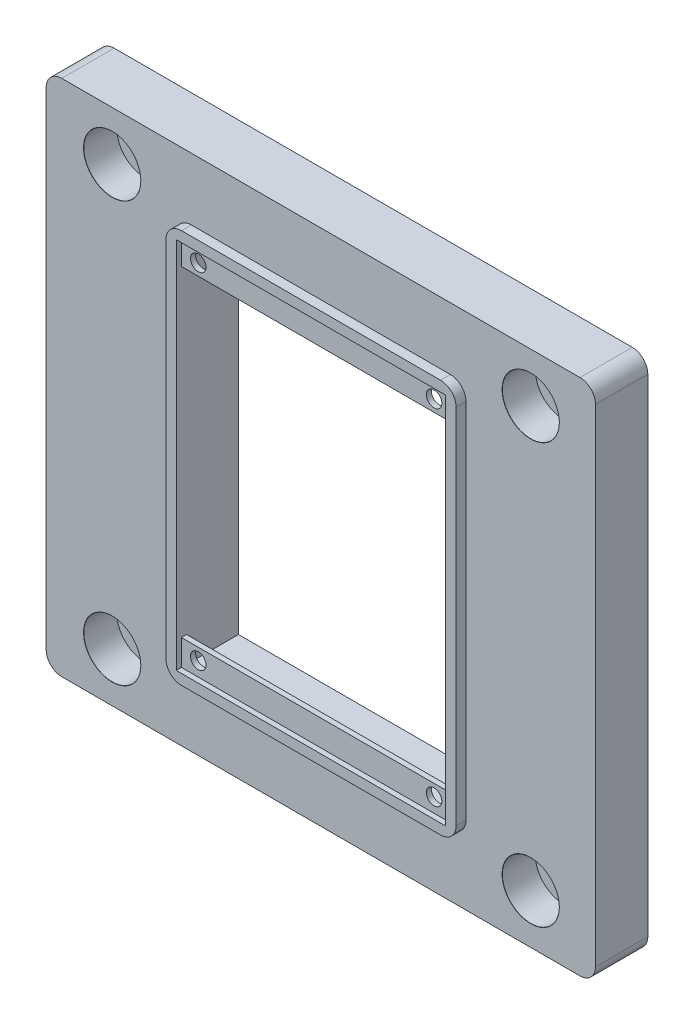
SolidWorks part; units mm, degrees
ref_plane "Front Plane" through (0, 0, 0) normal (1, 0, 0) x (0, 1, 0)
ref_plane "Top Plane" through (0, 0, 0) normal (0, 0, 1) x (0, 1, 0)
ref_plane "Right Plane" through (0, 0, 0) normal (0, 1, 0) x (-1, 0, 0)
sketch "Sketch1" plane through (0, 0, 0) normal (0, 0, 1) x (0, 1, 0)
  line L0 (33.4102, -36.8483) -> (45.4102, -61.8483)
  line L1 (-39.5237, 16.1988) -> (30.4763, 16.1988)
  line L2 (-39.5237, 16.1988) -> (-39.5237, -33.8012)
  line L3 (-39.5237, -33.8012) -> (30.4763, -33.8012)
  line L4 (30.4763, 16.1988) -> (30.4763, -33.8012)
  line L5 (-40.5898, 17.1517) -> (31.4102, 17.1517)
  line L6 (-40.5898, 17.1517) -> (-40.5898, -34.8483)
  line L7 (-40.5898, -34.8483) -> (31.4102, -34.8483)
  line L8 (31.4102, 17.1517) -> (31.4102, -34.8483)
  line L9 (-40.5898, 17.1517) -> (31.4102, -34.8483) construction
  line L10 (-40.5898, -34.8483) -> (31.4102, 17.1517) construction
  line L11 (-42.5898, -36.8483) -> (33.4102, -36.8483)
  line L12 (-42.5898, -36.8483) -> (-42.5898, 19.1517)
  line L13 (-42.5898, 19.1517) -> (33.4102, 19.1517)
  line L14 (33.4102, -36.8483) -> (33.4102, 19.1517)
  line L15 (-42.5898, -36.8483) -> (33.4102, 19.1517) construction
  line L16 (-42.5898, 19.1517) -> (33.4102, -36.8483) construction
  line L17 (-54.5898, 44.1517) -> (45.4102, 44.1517)
  line L18 (-54.5898, 44.1517) -> (-54.5898, -61.8483)
  line L19 (-54.5898, -61.8483) -> (45.4102, -61.8483)
  line L20 (45.4102, 44.1517) -> (45.4102, -61.8483)
  line L21 (-54.5898, 44.1517) -> (45.4102, -61.8483) construction
  line L22 (-54.5898, -61.8483) -> (45.4102, 44.1517) construction
  line L23 (45.4102, 44.1517) -> (33.4102, 19.1517)
  line L24 (39.4102, 31.6517) -> (39.4102, -49.3483)
  line L25 (39.4102, -49.3483) -> (39.4102, -61.8483)
  point P4 (-4.5898, -8.8483)
  point P9 (-4.5898, -8.8483)
  point P14 (-4.5898, -8.8483)
  point P21 (0, 0)
  point P23 (0, 0)
  point P24 (0, 0)
  point P25 (0, 0)
  point P26 (0, 0)
  dimension "D1" = 70
  dimension "D2" = 50
  dimension "D3" = 52
  dimension "D4" = 72
  dimension "D5" = 56
  dimension "D6" = 76
  dimension "D7" = 12.5
  dimension "D8" = 100
extrude "Boss-Extrude3" add sketch "Sketch1" along normal blind 10 and the other way blind 0.1 contours L20 L17 L18 L19 L14 L11 L12 L13 | L23 L24 L0 L20 | L24 L23 L14 L0 | L0 L25 L19 region at (8.8483, 36.5926, 0) region at (43.7289, 35.0964, 0) region at (8.8483, 42.5439, 0) region at (57.6817, 41.4102, 0)
sketch "Sketch5" plane through (0, 0, 10) normal (0, 0, 1) x (1, 0, 0)
  line L0 (49.3483, 39.4102) -> (49.3483, 35.9102)
  line L2 (-19.1517, -4.5898) -> (36.8483, -4.5898)
  line L3 (-19.1517, -42.5898) -> (-19.1517, 33.4102) construction
  line L4 (36.8483, -42.5898) -> (36.8483, 33.4102) construction
  point P1 (49.3483, 35.9102)
  point P6 (-31.4169, 35.9102)
  point P17 (-31.4169, -45.0898)
  point P18 (49.3483, -45.0898)
  dimension "D1" = 3.5
hole_wizard "CBORE for M6 Hex Socket Head Cap Screw2" positions "Sketch5" profile "Sketch6" counterbore size "M6" standard "ISO" end condition through all
sketch "Sketch6" plane through (49.3483, -45.0898, 10) normal (1, 0, 0) x (0, -1, 0)
  line L0 (0, 0) -> (0, 10.1)
  line L1 (0, 10.1) -> (3.3, 10.1)
  line L3 (3.3, 10.1) -> (3.3, 6.4)
  line L4 (5.5, 6.4) -> (3.3, 6.4)
  line L5 (5.5, 6.4) -> (5.5, 0.025)
  line L6 (5.5, 0.025) -> (5.525, 0)
  line L7 (5.525, 0) -> (0, 0)
  line L8 (-5.5, 0.025) -> (-5.525, 0) construction
  line L11 (0, -6.35) -> (0, 107.95) construction
  dimension "Thru Hole Dia." = 6.6
  dimension "Thru Hole Depth" = 10.1
  dimension "C'Bore Dia." = 11
  dimension "C'Bore Depth" = 6.4
  dimension "Near C'Sink Dia." = 11.05
  dimension "Near C'Sink Angle" = 90
sketch "Sketch7" plane through (0, 0, -0.1) normal (0, 0, -1) x (1, 0, 0)
  line L1 (-19.1517, 42.5898) -> (36.8483, 42.5898)
  line L2 (-19.1517, 42.5898) -> (-19.1517, -33.4102)
  line L3 (-19.1517, -33.4102) -> (36.8483, -33.4102)
  line L4 (36.8483, 42.5898) -> (36.8483, -33.4102)
extrude "Boss-Extrude4" add sketch "Sketch7" against normal blind 12
sketch "Sketch8" plane through (0, 0, 11.9) normal (0, 0, 1) x (1, 0, 0)
  line L1 (-17.1517, 31.4102) -> (34.8483, 31.4102)
  line L2 (-17.1517, 31.4102) -> (-17.1517, -40.5898)
  line L3 (-17.1517, -40.5898) -> (34.8483, -40.5898)
  line L4 (34.8483, 31.4102) -> (34.8483, -40.5898)
extrude "Boss-Extrude5" add sketch "Sketch8" against normal blind 1
sketch "Sketch9" plane through (0, 0, 11.9) normal (0, 0, 1) x (1, 0, 0)
  line L1 (-17.1517, 31.4102) -> (34.8483, 31.4102)
  line L2 (-17.1517, 31.4102) -> (-17.1517, -40.5898)
  line L3 (-17.1517, -40.5898) -> (34.8483, -40.5898)
  line L4 (34.8483, 31.4102) -> (34.8483, -40.5898)
extrude "Cut-Extrude1" cut sketch "Sketch9" against normal blind 1
sketch "Sketch10" plane through (0, 0, 10.9) normal (0, 0, 1) x (1, 0, 0)
  line L0 (34.8483, -40.5898) -> (34.8483, 31.4102) construction
  line L1 (-17.1517, 31.4102) -> (34.8483, 31.4102)
  line L2 (-17.1517, 31.4102) -> (-17.1517, 26.4148)
  line L3 (-17.1517, 26.4148) -> (34.8483, 26.4148)
  line L4 (34.8483, 31.4102) -> (34.8483, 26.4148)
  line L5 (-17.1517, -40.5898) -> (-17.1517, 31.4102) construction
  line L6 (34.8483, -40.5898) -> (-17.1517, -40.5898)
  line L7 (34.8483, -40.5898) -> (34.8483, -35.5907)
  line L8 (34.8483, -35.5907) -> (-17.1517, -35.5907)
  line L9 (-17.1517, -40.5898) -> (-17.1517, -35.5907)
  line L11 (-17.1517, 26.4148) -> (34.8483, 26.4148)
  line L12 (-17.1517, 26.4148) -> (-17.1517, -35.5907)
  line L13 (-17.1517, -35.5907) -> (34.8483, -35.5907)
  line L14 (34.8483, 26.4148) -> (34.8483, -35.5907)
  line M1 (-17.1517, 31.4102) -> (-17.1517, -40.5898)
  line M3 (34.8483, -40.5898) -> (34.8483, 31.4102)
extrude "Cut-Extrude2" cut sketch "Sketch10" against normal blind 11 contours L8 L3 M3 M1 region at (8.8483, -4.5879, 10.9)
sketch "Sketch11" plane through (0, 0, -0.1) normal (0, 0, -1) x (1, 0, 0)
  line L1 (-17.1517, 40.5898) -> (34.8483, 40.5898)
  line L2 (-17.1517, 40.5898) -> (-17.1517, 35.5907)
  line L3 (-17.1517, 35.5907) -> (34.8483, 35.5907)
  line L4 (34.8483, 40.5898) -> (34.8483, 35.5907)
  line L5 (-17.1517, -26.4148) -> (34.8483, -26.4148)
  line L6 (-17.1517, -26.4148) -> (-17.1517, -31.4102)
  line L7 (-17.1517, -31.4102) -> (34.8483, -31.4102)
  line L8 (34.8483, -26.4148) -> (34.8483, -31.4102)
extrude "Cut-Extrude3" cut sketch "Sketch11" against normal blind 10 contours L2 L1 L4 L3 | L6 L5 L8 L7
sketch "Sketch12" plane through (0, 0, 10.9) normal (0, 0, 1) x (1, 0, 0)
  line L0 (34.8483, -40.5898) -> (-17.1517, 31.4102) construction
  line L1 (-13.9017, 28.6602) -> (31.5983, 28.6602)
  line L2 (-13.9017, 28.6602) -> (-13.9017, -37.8398)
  line L3 (-13.9017, -37.8398) -> (31.5983, -37.8398)
  line L4 (31.5983, 28.6602) -> (31.5983, -37.8398)
  line L5 (-13.9017, 28.6602) -> (31.5983, -37.8398) construction
  line L6 (-13.9017, -37.8398) -> (31.5983, 28.6602) construction
  line L7 (-13.9017, -4.5898) -> (31.5983, -4.5898)
  line L8 (8.8483, 28.6602) -> (8.8483, -37.8398)
  circle A0 centre (-13.9017, -37.8398) radius 1.5
  circle A1 centre (31.5983, -37.8398) radius 1.5
  circle A2 centre (-13.9017, 28.6602) radius 1.5
  circle A3 centre (31.5983, 28.6602) radius 1.5
  point P0 (8.8483, -4.5898)
  point P15 (0, 0)
  dimension "D3" = 3
  dimension "D4" = 3
  dimension "D5" = 3
  dimension "D6" = 3
  dimension "D1" = 45.5
  dimension "D2" = 66.5
extrude "Cut-Extrude4" cut sketch "Sketch12" against normal blind 2 contours A2
extrude "Cut-Extrude5" cut sketch "Sketch12<3>" against normal blind 2 contours A3
sketch "Sketch12<3>" plane through (0, 0, 10.9) normal (0, 0, 1) x (1, 0, 0) same geometry as "Sketch12"
sketch "Sketch14" plane through (0, 0, 10.9) normal (0, 0, 1) x (1, 0, 0)
  circle A0 centre (-13.9017, -37.8398) radius 1.5
extrude "Cut-Extrude6" cut sketch "Sketch14" against normal blind 2
sketch "Sketch15" plane through (0, 0, 10.9) normal (0, 0, 1) x (1, 0, 0)
  circle A0 centre (31.5983, -37.8398) radius 1.5
extrude "Cut-Extrude7" cut sketch "Sketch15" against normal blind 2
fillet "Fillet2" radius 3 8 edges at (-44.1517, 45.4102, 4.95) (-19.1517, 33.4102, 10.95) (36.8483, 33.4102, 10.95) (61.8483, 45.4102, 4.95) (36.8483, -42.5898, 10.95) (61.8483, -54.5898, 4.95) (-44.1517, -54.5898, 4.95) (-19.1517, -42.5898, 10.95)
